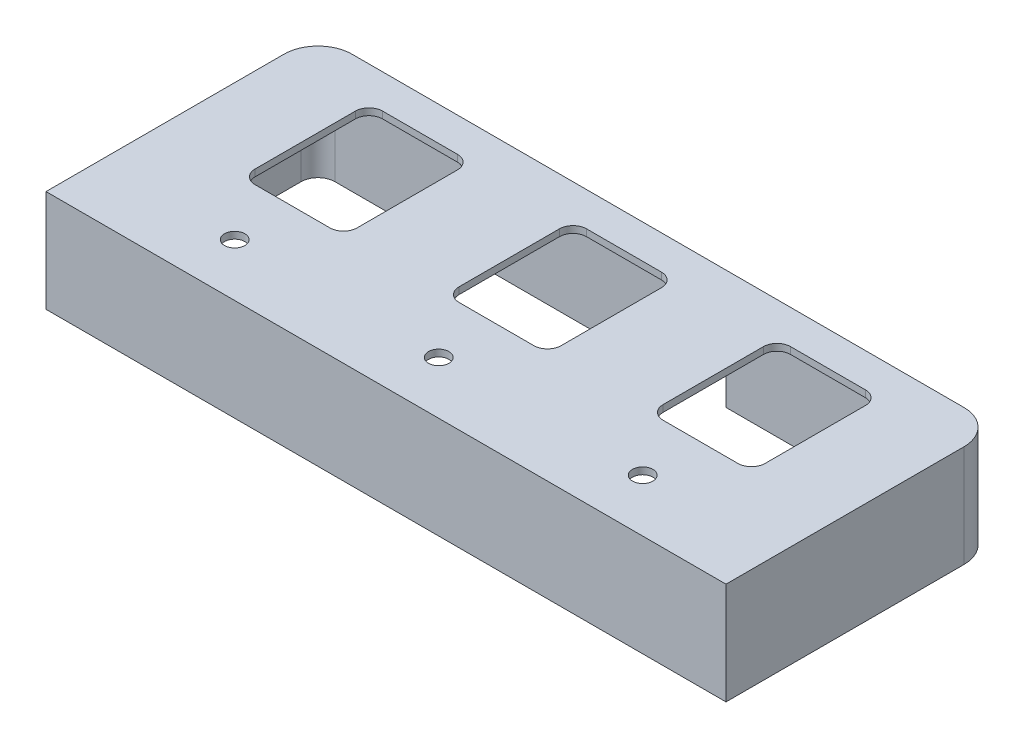
SolidWorks part; units mm, degrees
material "Калифорния"
ref_plane "Спереди" through (0, 0, 0) normal (0, 0, 1) x (1, 0, 0)
ref_plane "Сверху" through (0, 0, 0) normal (0, 1, 0) x (1, 0, 0)
ref_plane "Справа" through (0, 0, 0) normal (1, 0, 0) x (0, 0, -1)
sketch "Эскиз лицевой стороны" plane through (0, 0, 0) normal (0, 1, 0) x (1, 0, 0)
  line L0 (49, 30) -> (71, 30)
  line L1 (-90, 40) -> (90, 40)
  line L2 (-100, 30) -> (-100, -40)
  line L3 (-100, -40) -> (100, -40)
  line L4 (100, 30) -> (100, -40)
  line L5 (45, 26) -> (45, -3.5)
  line L6 (49, -7.5) -> (71, -7.5)
  line L7 (75, 26) -> (75, -3.5)
  line L8 (-11, 30) -> (11, 30)
  line L9 (-15, 26) -> (-15, -3.5)
  line L10 (-11, -7.5) -> (11, -7.5)
  line L11 (15, 26) -> (15, -3.5)
  line L12 (-71, 30) -> (-49, 30)
  line L13 (-75, 26) -> (-75, -3.5)
  line L14 (-71, -7.5) -> (-49, -7.5)
  line L15 (-45, 26) -> (-45, -3.5)
  line L16 (49, 30) -> (-11, 30) construction
  arc A2 (90, 40) -> (100, 30) centre (90, 30) cw
  arc A3 (-90, 40) -> (-100, 30) centre (-90, 30) ccw
  arc A4 (45, -3.5) -> (49, -7.5) centre (49, -3.5) ccw
  arc A5 (71, -7.5) -> (75, -3.5) centre (71, -3.5) ccw
  arc A6 (71, 30) -> (75, 26) centre (71, 26) cw
  arc A7 (49, 30) -> (45, 26) centre (49, 26) ccw
  arc A8 (-15, -3.5) -> (-11, -7.5) centre (-11, -3.5) ccw
  arc A9 (11, -7.5) -> (15, -3.5) centre (11, -3.5) ccw
  arc A10 (11, 30) -> (15, 26) centre (11, 26) cw
  arc A11 (-11, 30) -> (-15, 26) centre (-11, 26) ccw
  arc A12 (-75, -3.5) -> (-71, -7.5) centre (-71, -3.5) ccw
  arc A13 (-49, -7.5) -> (-45, -3.5) centre (-49, -3.5) ccw
  arc A14 (-49, 30) -> (-45, 26) centre (-49, 26) cw
  arc A15 (-71, 30) -> (-75, 26) centre (-71, 26) ccw
  circle A16 centre (60, -24.5) radius 3
  circle A17 centre (0, -24.5) radius 3
  circle A18 centre (-60, -24.5) radius 3
  point P8 (-100, -40)
  point P13 (100, 40)
  point P16 (-100, 40)
  dimension "D6" = 4
  dimension "D13" = 6
  dimension "D5" = 10
  dimension "D1" = 200
  dimension "D2" = 80
  dimension "D3" = 100
  dimension "D4" = 40
  dimension "D7" = 30
  dimension "D8" = 37.5
  dimension "D10" = 10
  dimension "D9" = 45
  dimension "D12" = 60
  dimension "D14" = 15
  dimension "D15" = 17
  dimension "D11" = 3
extrude "Лицевая сторона" add sketch "Эскиз лицевой стороны" against normal blind 2
sketch "Эскиз стенок" plane through (0, 0, 0) normal (0, 1, 0) x (1, 0, 0)
  line L0 (-90, 40) -> (90, 40)
  line L1 (-100, 30) -> (-100, -40)
  line L2 (-100, -40) -> (100, -40)
  line L3 (100, 30) -> (100, -40)
  line L13 (-90, 35) -> (90, 35)
  line L14 (95, 30) -> (95, -35)
  line L15 (-95, -35) -> (95, -35)
  line L16 (-95, 30) -> (-95, -35)
  arc A8 (100, 30) -> (90, 40) centre (90, 30) ccw
  arc A9 (-100, 30) -> (-90, 40) centre (-90, 30) cw
  arc A12 (95, 30) -> (90, 35) centre (90, 30) ccw
  arc A13 (-95, 30) -> (-90, 35) centre (-90, 30) cw
  dimension "D1" = 10
  dimension "D2" = 200
  dimension "D3" = 80
  dimension "D4" = 100
  dimension "D5" = 40
  dimension "D6" = 5
extrude "Стенки" add sketch "Эскиз стенок" against normal blind 30
ref_plane "Плоскость кабель-канала" through (0, -30, 0) normal (0, 1, 0) x (1, 0, 0)
sketch "Эскиз кабель-канала" plane through (0, -30, 0) normal (0, 1, 0) x (1, 0, 0)
  line L0 (90, 40) -> (-90, 40) construction
  line L1 (-5, 40) -> (25, 40)
  line L2 (-5, 40) -> (-5, 35)
  line L3 (-5, 35) -> (25, 35)
  line L4 (25, 40) -> (25, 35)
  line L5 (90, 35) -> (-90, 35) construction
  dimension "D1" = 30
  dimension "D2" = 5
extrude "Кабель-канал" cut sketch "Эскиз кабель-канала" along normal blind 10
equation "\"width\"= 200мм"
equation "\"height\"= 80мм"
equation "\"D1@Эскиз лицевой стороны\"=\"width\""
equation "\"D2@Эскиз лицевой стороны\"=\"height\""
equation "\"D4@Эскиз лицевой стороны\"=\"height\"/2"
equation "\"D3@Эскиз лицевой стороны\"=\"width\"/2"
equation "\"D2@Эскиз стенок\"=\"width\""
equation "\"D3@Эскиз стенок\"=\"height\""
equation "\"external_radius\"= 10.00мм"
equation "\"D1@Эскиз стенок\"=\"external_radius\""
equation "\"D5@Эскиз лицевой стороны\"=\"external_radius\""
